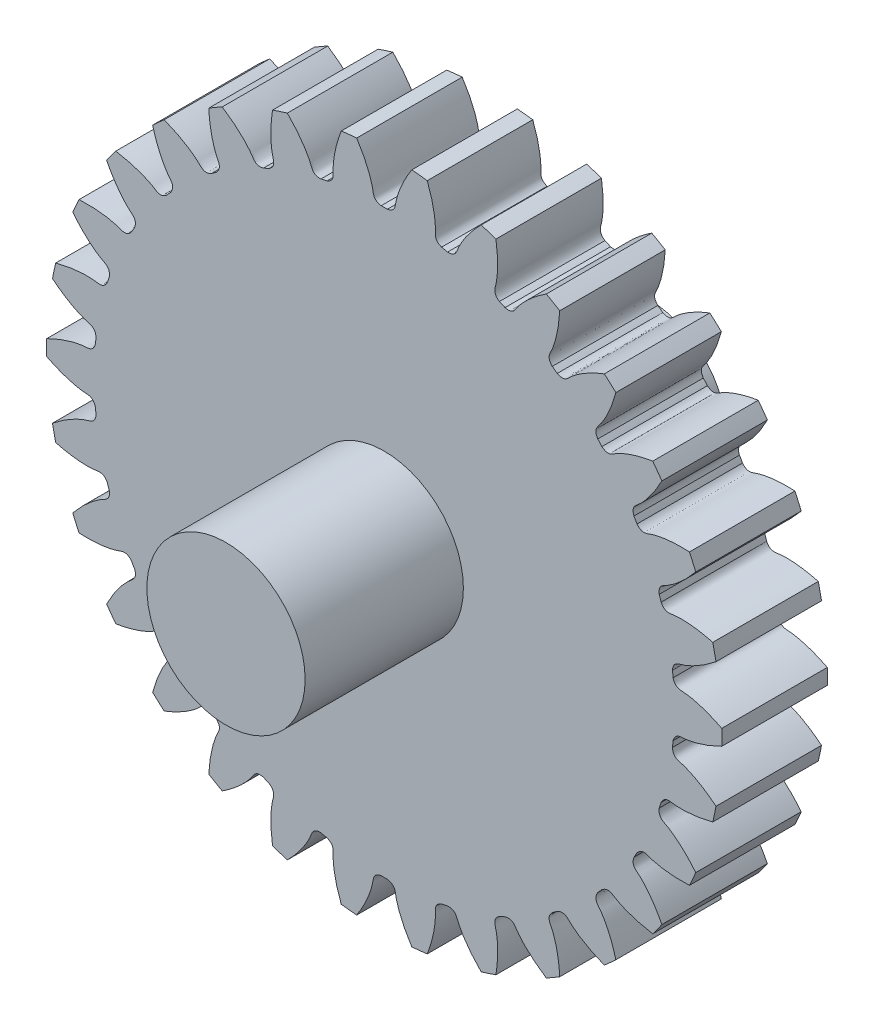
SolidWorks part; units mm, degrees
ref_plane "前视基准面" through (0, 0, 0) normal (0, 0, 1) x (1, 0, 0)
ref_plane "上视基准面" through (0, 0, 0) normal (0, 1, 0) x (1, 0, 0)
ref_plane "右视基准面" through (0, 0, 0) normal (1, 0, 0) x (0, 0, -1)
sketch "草图1" plane through (0, 0, 0) normal (0, 0, 1) x (1, 0, 0)
  circle A0 centre (0, 0) radius 32
extrude "凸台-拉伸1" add sketch "草图1" along normal blind 10
ref_axis "基准轴1" through (0, 0, 10) along (0, 0, -1)
sketch "草图2" plane through (0, 0, 0) normal (0, 0, 1) x (1, 0, 0)
  line L0 (0, 0) -> (0, 32) construction
  circle A0 centre (0, 0) radius 32 construction
  arc A1 (0.2911, 27.4985) -> (-0.2911, 27.4985) centre (0, 0) ccw
  arc A2 (6.7326, 36.3811) -> (-6.7326, 36.3811) centre (0, 0) ccw
  spline S0 degree 3 poles (0.2911, 27.4985) (1.0165, 27.626) (1.0206, 28.0943) (1.118, 28.5772) (1.1399, 28.6763) (1.1665, 28.7858) (1.1981, 28.9058) (1.2353, 29.0359) (1.2783, 29.1761) (1.3276, 29.326) (1.3837, 29.4856) (1.4469, 29.6547) (1.5176, 29.8328) (1.5962, 30.02) (1.6832, 30.2158) (1.7788, 30.4201) (1.8834, 30.6325) (1.9975, 30.8529) (2.1213, 31.0808) (2.2552, 31.3159) (2.3996, 31.5581) (2.5548, 31.8069) (2.7211, 32.0619) (2.8987, 32.323) (3.0881, 32.5896) (3.2895, 32.8614) (3.5032, 33.1381) (3.7295, 33.4192) (3.9685, 33.7044) (4.2207, 33.9933) (4.4861, 34.2854) (4.7651, 34.5803) (5.0578, 34.8776) (5.3645, 35.1769) (5.6854, 35.4777) (6.1378, 35.8852) (6.4907, 36.1841) (6.7326, 36.3811) knots 0 0 0 0 0.115324 0.123413 0.132512 0.142623 0.153745 0.165878 0.179022 0.193177 0.208343 0.22452 0.241708 0.259907 0.279117 0.299338 0.320571 0.342814 0.366068 0.390334 0.41561 0.441898 0.469196 0.497506 0.526827 0.557158 0.588501 0.620855 0.65422 0.688595 0.723982 0.76038 0.797789 0.836209 0.87564 0.916083 1 1 1 1
  spline S1 degree 3 poles (-0.2911, 27.4985) (-1.0165, 27.626) (-1.0206, 28.0943) (-1.118, 28.5772) (-1.1399, 28.6763) (-1.1665, 28.7858) (-1.1981, 28.9058) (-1.2353, 29.0359) (-1.2783, 29.1761) (-1.3276, 29.326) (-1.3837, 29.4856) (-1.4469, 29.6547) (-1.5176, 29.8328) (-1.5962, 30.02) (-1.6832, 30.2158) (-1.7788, 30.4201) (-1.8834, 30.6325) (-1.9975, 30.8529) (-2.1213, 31.0808) (-2.2552, 31.3159) (-2.3996, 31.5581) (-2.5548, 31.8069) (-2.7211, 32.0619) (-2.8987, 32.323) (-3.0881, 32.5896) (-3.2895, 32.8614) (-3.5032, 33.1381) (-3.7295, 33.4192) (-3.9685, 33.7044) (-4.2207, 33.9933) (-4.4861, 34.2854) (-4.7651, 34.5803) (-5.0578, 34.8776) (-5.3645, 35.1769) (-5.6854, 35.4777) (-6.1378, 35.8852) (-6.4907, 36.1841) (-6.7326, 36.3811) knots 0 0 0 0 0.115324 0.123413 0.132512 0.142623 0.153745 0.165878 0.179022 0.193177 0.208343 0.22452 0.241708 0.259907 0.279117 0.299338 0.320571 0.342814 0.366068 0.390334 0.41561 0.441898 0.469196 0.497506 0.526827 0.557158 0.588501 0.620855 0.65422 0.688595 0.723982 0.76038 0.797789 0.836209 0.87564 0.916083 1 1 1 1
extrude "切除-拉伸1" cut sketch "草图2" along normal through all
pattern_circular "阵列(圆周)1" count 30 every 12 about axis through (0, 0, 10) along (0, 0, -1) of "切除-拉伸1"
sketch "草图3" plane through (0, 0, 0) normal (0, 0, 1) x (1, 0, 0)
  circle A0 centre (0, 0) radius 30 construction
  dimension "Dn" = 60
sketch "草图4" plane through (0, 0, 10) normal (0, 0, 1) x (1, 0, 0)
  circle A0 centre (0, 0) radius 7.5
  dimension "D1" = 15
extrude "凸台-拉伸2" add sketch "草图4" along normal blind 15
sketch "草图5" plane through (0, 0, 0) normal (0, 0, -1) x (-1, 0, 0)
  circle A0 centre (0, 0) radius 7.5
  dimension "D1" = 15
extrude "凸台-拉伸3" add sketch "草图5" along normal blind 15
